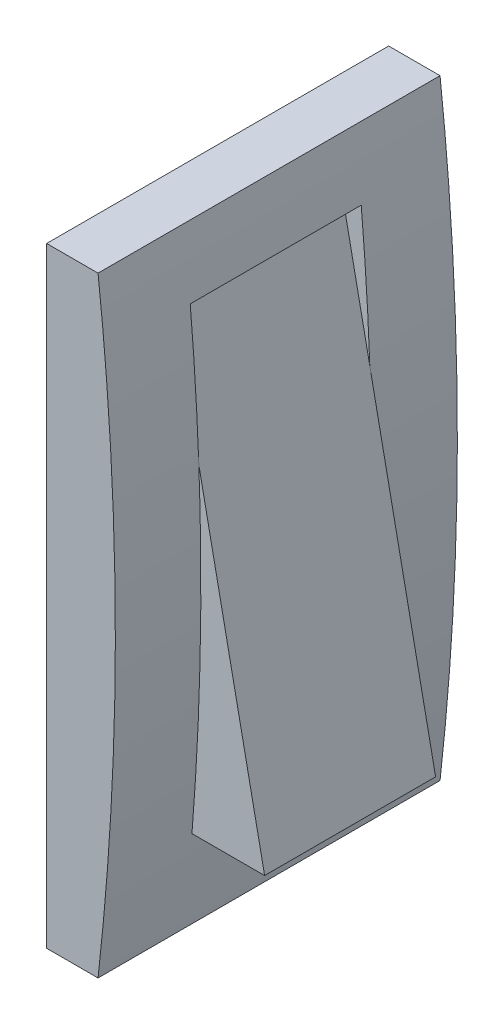
SolidWorks part; units mm, degrees
ref_plane "Front Plane" through (0, 0, 0) normal (0, 0, 1) x (1, 0, 0)
ref_plane "Top Plane" through (0, 0, 0) normal (0, 1, 0) x (1, 0, 0)
ref_plane "Right Plane" through (0, 0, 0) normal (1, 0, 0) x (0, 0, -1)
sketch "Sketch1" plane through (0, 0, 0) normal (1, 0, 0) x (0, 0, -1)
  line L1 (-19.6489, -35.6975) -> (19.6489, -35.6975)
  line L2 (-19.6489, -35.6975) -> (-19.6489, 35.6975)
  line L3 (-19.6489, 35.6975) -> (19.6489, 35.6975)
  line L4 (19.6489, -35.6975) -> (19.6489, 35.6975)
  line L5 (-19.6489, -35.6975) -> (19.6489, 35.6975) construction
  line L6 (-19.6489, 35.6975) -> (19.6489, -35.6975) construction
  point P0 (0, 0)
sketch "Sketch2" plane through (0, 0, 0) normal (0, 0, 1) x (1, 0, 0)
  line L0 (0, -35.6975) -> (0, 35.6975)
  line L1 (0, -35.6975) -> (0, 35.6975) construction
  line L2 (0, -35.6975) -> (0, 35.6975) construction
  line L3 (0, 35.6975) -> (6.0094, 35.6975)
  line L4 (0, -35.6975) -> (6.0094, -35.6975)
  spline S0 degree 2 poles (6.0094, 35.6975) (10.0568, 0) (6.0094, -35.6975) knots 0 0 0 1 1 1
  point P9 (8.0331, 0)
extrude "Boss-Extrude1" add sketch "Sketch2" along normal blind 20 and the other way blind 20
sketch "Sketch3" plane through (0, 0, 0) normal (0, 0, 1) x (1, 0, 0)
  line L0 (4.5783, 27.9738) -> (4.5783, -25.5796)
  line L3 (4.5783, -25.5796) -> (15.4907, -25.5796)
  line L4 (15.4907, -25.5796) -> (4.5783, 27.9738)
  point P2 (0, 0)
  point P3 (4.5783, 27.9738)
  point P4 (4.5783, -25.5796)
  point P10 (6.994, 27.9397)
sketch "Sketch4" plane through (0, 0, 0) normal (0, 0, 1) x (1, 0, 0)
  line L1 (4.5783, 27.9738) -> (15.4907, 27.9738)
  line L2 (4.5783, 27.9738) -> (4.5783, -25.5796)
  line L3 (4.5783, -25.5796) -> (15.4907, -25.5796)
  line L4 (15.4907, 27.9738) -> (15.4907, -25.5796)
extrude "Cut-Extrude1" cut sketch "Sketch4" against normal blind 10 and the other way blind 10
extrude "Boss-Extrude2" add sketch "Sketch3" along normal blind 10 and the other way blind 10
sketch3d "URDF Reference"
  line L0 (0, 0, 0) -> (10, 0, 0) construction
  line L1 (0, 0, 0) -> (0, 0, -10) construction
  point P0 (0, 0, 0)
  point P1 (0, 0, 0)
